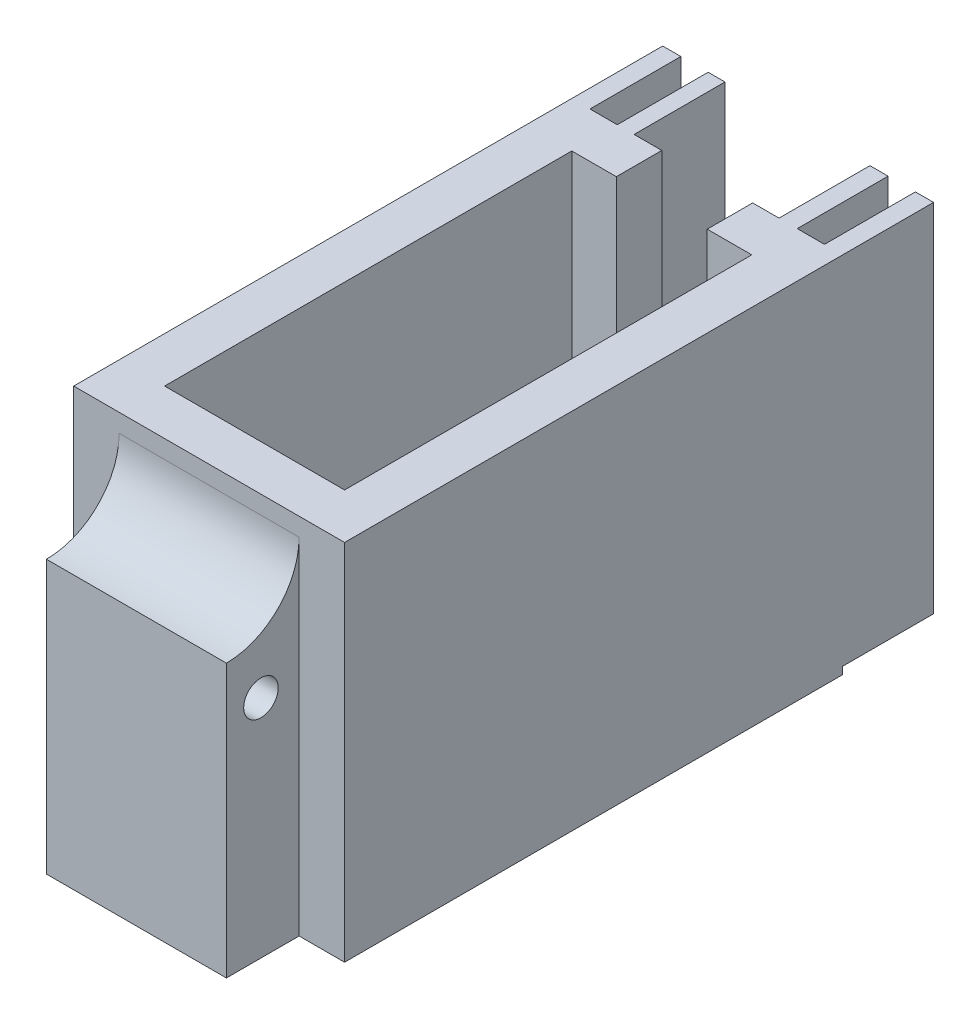
SolidWorks part; units mm, degrees
ref_plane "Front Plane" through (0, 0, 0) normal (0, 0, 1) x (1, 0, 0)
ref_plane "Top Plane" through (0, 0, 0) normal (0, 1, 0) x (1, 0, 0)
ref_plane "Right Plane" through (0, 0, 0) normal (1, 0, 0) x (0, 0, -1)
sketch "Sketch1" plane through (0, 0, 0) normal (0, 1, 0) x (1, 0, 0)
  line L0 (-24.306, 0.8435) -> (-24.306, -56.0525)
  line L1 (-24.306, -56.0525) -> (0.84, -56.0525)
  line L2 (0.84, -56.0525) -> (0.84, 0.8435)
  line L3 (0.84, 0.8435) -> (-24.306, 0.8435)
  line L4 (-11.733, 0.8435) -> (-11.733, 7.1935)
  line L5 (-24.306, -27.6045) -> (-30.656, -27.6045)
  line L6 (-30.656, -27.6045) -> (-30.656, 7.1935)
  line L7 (-30.656, 7.1935) -> (-11.733, 7.1935)
  line L8 (-11.733, 7.1935) -> (7.19, 7.1935)
  line L9 (7.19, 7.1935) -> (7.19, -62.4025)
  line L10 (7.19, -62.4025) -> (-30.656, -62.4025)
  line L11 (-30.656, -27.6045) -> (-30.656, -62.4025)
  dimension "D1" = 56.896
  dimension "D2" = 25.146
  dimension "D3" = 6.35
  dimension "D4" = 6.35
extrude "Boss-Extrude1" add sketch "Sketch1" along normal blind 50.8 contours L5 L11 L10 L9 L8 L4 L3 L2 L1 L0 | L7 L6 L5 L0 L3 L4 region at (-24.9698, 0, 6.4302) region at (-25.0982, 0, 41.8285)
sketch "Sketch3" plane through (0, 0, -7.1935) normal (0, 0, -1) x (-1, 0, 0)
  line L0 (11.733, 0) -> (11.733, 29.21)
  line L1 (30.656, 0) -> (-7.19, 0) construction
  line L2 (11.733, 29.21) -> (5.383, 29.21)
  line L3 (5.383, 29.21) -> (5.383, 50.8)
  line L4 (5.383, 50.8) -> (18.083, 50.8)
  line L5 (18.083, 50.8) -> (18.083, 29.21)
  line L6 (18.083, 29.21) -> (11.733, 29.21)
  line L7 (18.083, 29.21) -> (11.733, 29.21)
  line L8 (30.656, 50.8) -> (-7.19, 50.8) construction
  line M7 (30.656, 50.8) -> (-7.19, 50.8)
  dimension "D1" = 29.21
  dimension "D2" = 6.35
extrude "Cut-Extrude1" cut sketch "Sketch3" against normal blind 50.8 and the other way through all contours L6 L5 L3 L2 M7 region at (-11.733, 40.005, -7.1935)
ref_plane "Plane1" through (0, 1.016, 0) normal (0, 1, 0) x (1, 0, 0)
sketch "Sketch4" plane through (0, 1.016, 0) normal (0, 1, 0) x (1, 0, 0)
  line L0 (-11.733, 7.1935) -> (-11.733, 11.7655)
  line L1 (-5.383, 7.1935) -> (-18.083, 7.1935) construction
  line L2 (-11.733, 11.7655) -> (-18.083, 11.7655)
  line L3 (-11.733, 11.7655) -> (-5.383, 11.7655)
  line L4 (-30.656, 7.1935) -> (-30.656, 19.8935)
  line L5 (-30.656, 19.8935) -> (7.19, 19.8935)
  line L6 (7.19, 19.8935) -> (7.19, 7.1935)
  line L7 (-16.051, 13.7975) -> (-7.415, 13.7975)
  line L8 (-18.083, 0.8435) -> (-5.383, 0.8435) construction
  line L9 (-30.656, 7.1935) -> (7.19, 7.1935)
  circle A0 centre (-18.083, 13.7975) radius 2.032
  circle A1 centre (-5.383, 13.7975) radius 2.032
  dimension "D1" = 4.064
  dimension "D2" = 10.922
  dimension "D3" = 8.636
  dimension "D4" = 12.7
extrude "Boss-Extrude2" add sketch "Sketch4" along normal blind 4.572 contours A1 L3 L9 L6 L5 L4 L2 A0 L7 | A1 L7 A0 L2 L3 region at (-11.733, 1.016, -12.7299) region at (-21.1945, 1.016, -7.5927)
sketch "Sketch7" plane through (0, 5.588, 0) normal (0, 1, 0) x (1, 0, 0)
  line L0 (7.19, 7.1935) -> (7.19, 19.8935)
  line L1 (7.19, 19.8935) -> (4.65, 19.8935)
  line L2 (-30.656, 19.8935) -> (7.19, 19.8935) construction
  line L3 (4.65, 19.8935) -> (4.65, 7.1935)
  line L4 (-30.656, 7.1935) -> (7.19, 7.1935) construction
  line L5 (4.65, 7.1935) -> (7.19, 7.1935)
  line L9 (-5.383, 7.1935) -> (7.19, 7.1935) construction
  line L10 (0.84, 7.1935) -> (0.84, 19.8935)
  line L12 (-30.656, 19.8935) -> (-30.656, 7.1935)
  line L13 (-30.656, 7.1935) -> (-28.116, 7.1935)
  line L14 (-30.656, 7.1935) -> (-18.083, 7.1935) construction
  line L15 (-28.116, 7.1935) -> (-28.116, 19.8935)
  line L16 (-28.116, 19.8935) -> (-30.656, 19.8935)
  line L17 (0.84, 19.8935) -> (-1.7, 19.8935)
  line L18 (-1.7, 19.8935) -> (-1.7, 7.1935)
  line L19 (-1.7, 7.1935) -> (0.84, 7.1935)
  line L20 (-24.306, 7.1935) -> (-24.306, 19.8935)
  line L21 (-24.306, 19.8935) -> (-21.9525, 19.8935)
  line L22 (-21.9525, 19.8935) -> (-21.9525, 7.1935)
  line L23 (-21.9525, 7.1935) -> (-24.306, 7.1935)
  line L24 (-24.306, 7.1935) -> (-28.116, 7.1935)
  line L25 (4.65, 7.1935) -> (0.84, 7.1935)
  line M12 (-30.656, 19.8935) -> (-30.656, 7.1935)
  line M13 (-30.656, 7.1935) -> (7.19, 7.1935)
  line M14 (7.19, 7.1935) -> (7.19, 19.8935)
  line M15 (7.19, 19.8935) -> (-30.656, 19.8935)
  dimension "D1" = 2.54
  dimension "D2" = 3.81
  dimension "D3" = 2.54
  dimension "D4" = 3.81
  dimension "D5" = 2.54
extrude "Boss-Extrude3" add sketch "Sketch7" along normal up to surface (45.212 mm away) contours L3 M15 M13 M14 | L18 L10 M15 M13 | L22 L20 M15 M13 | L15 M13 M15 M12 region at (5.92, 5.588, -13.5435) region at (-0.43, 5.588, -13.5435) region at (-23.1293, 5.588, -13.5435) region at (-29.386, 5.588, -13.5435) up to face at (-11.733, 50.8, 17.0635)
sketch "Sketch8" plane through (-30.656, 0, 0) normal (-1, 0, 0) x (0, 0, 1)
  line L0 (56.0525, 31.496) -> (71.5465, 31.496)
  line L1 (62.4025, 50.8) -> (56.0525, 50.8)
  line L2 (-19.8935, 50.8) -> (62.4025, 50.8) construction
  line L3 (56.0525, 50.8) -> (56.0525, 31.496)
  line L4 (71.5465, 31.496) -> (71.5465, 0)
  line L5 (71.5465, 0) -> (62.4025, 0)
  line L6 (62.4025, 0) -> (72.5625, 0)
  line L7 (72.5625, 0) -> (72.5625, 38.1)
  line L8 (72.5625, 38.1) -> (62.4025, 38.1)
  line L9 (62.4025, 50.8) -> (62.4025, 0) construction
  line L10 (62.4025, 38.1) -> (62.4025, -0.2472)
  circle A0 centre (67.7365, 31.496) radius 2.413
  line M8 (62.4025, 0) -> (62.4025, 50.8)
  dimension "D5" = 4.826
  dimension "D1" = 6.35
  dimension "D2" = 15.494
  dimension "D3" = 31.496
  dimension "D4" = 3.81
  dimension "D6" = 10.16
  dimension "D7" = 38.1
extrude "Boss-Extrude4" add sketch "Sketch8" against normal up to surface (37.846 mm away) contours A0 L0 L5 L4 M8 | A0 L0 L4 L6 L7 L8 M8 region at (-30.656, 34.3033, 67.7365) region at (-30.656, 15.2651, 66.9495)
fillet "Fillet1" radius 10.16 1 edges at (-11.733, 38.1, 62.4025)
sketch "Sketch9" plane through (0, 50.8, 0) normal (0, 1, 0) x (1, 0, 0)
  line L0 (-30.656, -62.4025) -> (-24.306, -62.4025)
  line L1 (-30.656, -62.4025) -> (7.19, -62.4025) construction
  line L2 (-24.306, -62.4025) -> (-24.306, -75.5867)
  line L3 (-24.306, -75.5867) -> (-30.656, -75.5867)
  line L4 (-30.656, -75.5867) -> (-30.656, -62.4025)
  line L5 (7.19, -62.4025) -> (0.84, -62.4025)
  line L6 (7.19, -62.4025) -> (-30.656, -62.4025) construction
  line L7 (0.84, -62.4025) -> (0.84, -76.2556)
  line L8 (0.84, -76.2556) -> (7.2958, -76.2556)
  line L9 (7.2958, -76.2556) -> (7.19, -62.4025)
  line L10 (-24.306, 0.8435) -> (-24.306, -56.0525) construction
  line L11 (0.84, -56.0525) -> (0.84, 0.8435) construction
extrude "Cut-Extrude2" cut sketch "Sketch9" against normal through all
